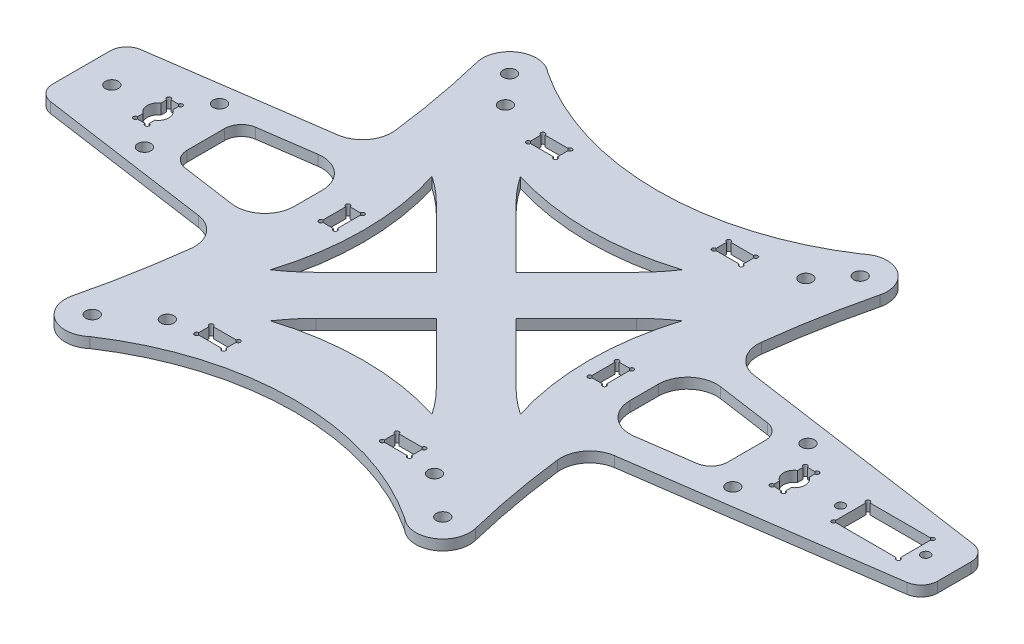
SolidWorks part; units mm, degrees
material "PPS"
ref_plane "前视基准面" through (0, 0, 0) normal (0, 0, 1) x (1, 0, 0)
ref_plane "上视基准面" through (0, 0, 0) normal (0, 1, 0) x (1, 0, 0)
ref_plane "右视基准面" through (0, 0, 0) normal (1, 0, 0) x (0, 0, -1)
sketch "草图1" plane through (0, 0, 0) normal (0, 1, 0) x (1, 0, 0)
  line L3 (-133.7177, 0) -> (146.3754, 0) construction
  line L56 (0, 96.0639) -> (0, -115.1457) construction
  line L65 (-25.5, 41.5) -> (-19, 41.5)
  line L66 (-34, 3.25) -> (-30.5, 3.25)
  line L70 (-34, 3.25) -> (-34, -3.25)
  line L76 (-34, -3.25) -> (-30.5, -3.25)
  line L80 (-30.5, 3.25) -> (-30.5, -3.25)
  line L81 (-25.5, -38) -> (-19, -38)
  line L82 (-25.5, -38) -> (-25.5, -41.5)
  line L83 (-25.5, -41.5) -> (-19, -41.5)
  line L84 (-19, -38) -> (-19, -41.5)
  line L85 (-19, 38) -> (-19, 41.5)
  line L86 (-25.5, 38) -> (-19, 38)
  line L142 (-25.5, 38) -> (-25.5, 41.5)
  line L143 (25.5, 38) -> (25.5, 41.5)
  line L144 (25.5, 38) -> (19, 38)
  line L145 (19, 38) -> (19, 41.5)
  line L146 (19, -38) -> (19, -41.5)
  line L147 (25.5, -41.5) -> (19, -41.5)
  line L148 (25.5, -38) -> (25.5, -41.5)
  line L149 (25.5, -38) -> (19, -38)
  line L150 (30.5, 3.25) -> (30.5, -3.25)
  line L151 (34, -3.25) -> (30.5, -3.25)
  line L152 (34, 3.25) -> (34, -3.25)
  line L153 (34, 3.25) -> (30.5, 3.25)
  line L154 (25.5, 41.5) -> (19, 41.5)
  line L155 (77.65, -2.1518) -> (77.65, -4)
  line L156 (74.85, 4) -> (77.65, 4)
  line L157 (74.85, 4) -> (74.85, 2.1768)
  line L158 (74.85, -4) -> (77.65, -4)
  line L159 (77.65, 4) -> (77.65, 2.1518)
  line L160 (74.85, -2.1768) -> (74.85, -4)
  line L161 (97.5, 7.6653) -> (97.5, -9.1503) construction
  line L162 (89.75, 4.1) -> (105.25, 4.1)
  line L163 (89.75, 4.1) -> (89.75, -4.1)
  line L164 (89.75, -4.1) -> (105.25, -4.1)
  line L165 (105.25, 4.1) -> (105.25, -4.1)
  line L166 (-97.5, 7.6653) -> (-97.5, -9.1503) construction
  line L171 (-74.85, -2.1768) -> (-74.85, -4)
  line L172 (-77.65, 4) -> (-77.65, 2.1518)
  line L173 (-74.85, -4) -> (-77.65, -4)
  line L174 (-74.85, 4) -> (-74.85, 2.1768)
  line L175 (-74.85, 4) -> (-77.65, 4)
  line L176 (-77.65, -2.1518) -> (-77.65, -4)
  line L177 (114.5911, 7.4683) -> (114.5911, -7.4683)
  line L178 (114.5911, 7.4683) -> (43.1936, 17.6463)
  line L179 (114.5911, -7.4683) -> (43.1936, -17.6463)
  line L183 (-23.978, 14.4296) -> (-9.5485, 0)
  line L184 (14.4296, 23.978) -> (0, 9.5485)
  line L185 (-23.978, -14.4296) -> (-9.5485, 0)
  line L186 (-14.4296, 23.978) -> (0, 9.5485)
  line L187 (23.978, -14.4296) -> (9.5485, 0)
  line L188 (23.978, 14.4296) -> (9.5485, 0)
  line L189 (-14.4296, -23.978) -> (0, -9.5485)
  line L190 (14.4296, -23.978) -> (0, -9.5485)
  line L191 (-94.5795, 10.321) -> (-94.5795, -10.321)
  line L192 (-43.1936, 17.6463) -> (-94.5795, 10.321)
  line L193 (-94.5795, -10.321) -> (-43.1936, -17.6463)
  line L195 (-64.75, -7.9571) -> (-64.75, 7.9571)
  line L196 (-64.75, 7.9571) -> (-40.25, 11.4497)
  line L197 (-40.25, 11.4497) -> (-40.25, -11.4497)
  line L198 (-64.75, -7.9571) -> (-40.25, -11.4497)
  line L199 (64.75, 7.9571) -> (40.25, 11.4497)
  line L200 (40.25, 11.4497) -> (40.25, -11.4497)
  line L201 (64.75, -7.9571) -> (40.25, -11.4497)
  line L202 (64.75, 7.9571) -> (64.75, -7.9571)
  circle A0 centre (-36, 43) radius 1.55
  circle A1 centre (-32, -42) radius 1.55
  circle A2 centre (32, -42) radius 1.55
  circle A3 centre (36, 43) radius 1.55
  circle A4 centre (42, 50) radius 1.55
  circle A5 centre (42, -50) radius 1.55
  circle A6 centre (-42, -50) radius 1.55
  circle A7 centre (-42, 50) radius 1.55
  arc A8 (74.85, 2.1768) -> (74.85, -2.1768) centre (76.2307, 0) ccw
  arc A9 (77.65, -2.1518) -> (77.65, 2.1518) centre (76.2307, 0) ccw
  circle A10 centre (107.7, 0) radius 1.05
  circle A11 centre (87.3, 0) radius 1.05
  circle A12 centre (-87.3, 0) radius 1.05 construction
  arc A14 (-77.65, -2.1518) -> (-77.65, 2.1518) centre (-76.2307, 0) cw
  arc A15 (-74.85, 2.1768) -> (-74.85, -2.1768) centre (-76.2307, 0) cw
  arc A18 (-37.7098, 54.831) -> (37.7098, 54.831) centre (0, 111.5317) ccw
  arc A20 (48.2756, 48.4632) -> (43.1936, 17.6463) centre (246.1791, 0) ccw
  arc A21 (48.2756, 48.4632) -> (37.7098, 54.831) centre (42, 50) ccw
  arc A22 (-37.7098, -54.831) -> (37.7098, -54.831) centre (0, -111.5317) cw
  arc A23 (48.2756, -48.4632) -> (43.1936, -17.6463) centre (246.1791, 0) cw
  arc A24 (48.2756, -48.4632) -> (37.7098, -54.831) centre (42, -50) cw
  arc A26 (-48.2756, -48.4632) -> (-37.7098, -54.831) centre (-42, -50) ccw
  arc A27 (-48.2756, -48.4632) -> (-43.1936, -17.6463) centre (-246.1791, 0) ccw
  arc A28 (-48.2756, 48.4632) -> (-37.7098, 54.831) centre (-42, 50) cw
  arc A30 (-48.2756, 48.4632) -> (-43.1936, 17.6463) centre (-246.1791, 0) cw
  arc A31 (-23.978, 14.4296) -> (-29.9602, 19.3706) centre (-52.8883, -14.4807) ccw
  arc A32 (-23.978, -14.4296) -> (-29.9602, -19.3706) centre (-52.8883, 14.4807) cw
  arc A33 (-29.9602, -19.3706) -> (-29.9602, 19.3706) centre (-91.9966, 0) ccw
  arc A34 (-14.4296, 23.978) -> (-19.3706, 29.9602) centre (14.4807, 52.8883) cw
  arc A35 (-19.3706, 29.9602) -> (19.3706, 29.9602) centre (0, 91.9966) ccw
  arc A36 (14.4296, 23.978) -> (19.3706, 29.9602) centre (-14.4807, 52.8883) ccw
  arc A37 (23.978, 14.4296) -> (29.9602, 19.3706) centre (52.8883, -14.4807) cw
  arc A38 (29.9602, 19.3706) -> (29.9602, -19.3706) centre (91.9966, 0) ccw
  arc A39 (23.978, -14.4296) -> (29.9602, -19.3706) centre (52.8883, 14.4807) ccw
  arc A40 (14.4296, -23.978) -> (19.3706, -29.9602) centre (-14.4807, -52.8883) cw
  arc A41 (19.3706, -29.9602) -> (-19.3706, -29.9602) centre (0, -91.9966) ccw
  arc A42 (-14.4296, -23.978) -> (-19.3706, -29.9602) centre (14.4807, -52.8883) ccw
  circle A43 centre (70.5, 9) radius 1.55
  circle A44 centre (70.5, -9) radius 1.55
  circle A45 centre (-70.5, -9) radius 1.55
  circle A46 centre (-70.5, 9) radius 1.55
  circle A47 centre (-87.3, 0) radius 1.55
  point P81 (-34, 0)
  point P118 (0, 0)
  point P140 (-40.25, 0)
  point P149 (-64.75, 0)
  dimension "D5" = 38
  dimension "D18" = 8.2
  dimension "D24" = 3.1
  dimension "D6" = 3.1
  dimension "D11" = 50
  dimension "D15" = 74.85
  dimension "D16" = 2.1
  dimension "D17" = 15.5
  dimension "D21" = 3.1
  dimension "D1" = 6.5
  dimension "D2" = 3.5
  dimension "D3" = 30.5
  dimension "D4" = 19
  dimension "D7" = 32
  dimension "D8" = 42
  dimension "D9" = 43
  dimension "D10" = 36
  dimension "D12" = 42
  dimension "D13" = 2.8
  dimension "D14" = 4
  dimension "D19" = 2.45
  dimension "D20" = 97.5
  dimension "D22" = 9
  dimension "D23" = 70.5
  dimension "D25" = 6.55
  dimension "D26" = 5.75
  dimension "D27" = 6.25
  dimension "D28" = 4
extrude "凸台-拉伸1" add sketch "草图1" along normal blind 2.5
fillet "圆角1" radius 4 8 edges at (114.5911, 1.25, -7.4683) (114.5911, 1.25, 7.4683) (-94.5795, 1.25, 10.321) (-94.5795, 1.25, -10.321) (-64.75, 1.25, 7.9571) (-64.75, 1.25, -7.9571) (64.75, 1.25, 7.9571) (64.75, 1.25, -7.9571)
fillet "圆角2" radius 7 8 edges at (43.1936, 1.25, -17.6463) (43.1936, 1.25, 17.6463) (-43.1936, 1.25, 17.6463) (-43.1936, 1.25, -17.6463) (40.25, 1.25, 11.4497) (40.25, 1.25, -11.4497) (-40.25, 1.25, 11.4497) (-40.25, 1.25, -11.4497)
sketch "草图2" plane through (0, 2.5, 0) normal (0, 1, 0) x (1, 0, 0)
  line L0 (0, 0) -> (0, -66.7571) construction
  circle A0 centre (-77.65, 4) radius 0.5
  circle A1 centre (-74.85, 4) radius 0.5
  circle A2 centre (-77.65, -4) radius 0.5
  circle A3 centre (-74.85, -4) radius 0.5
  circle A4 centre (-25.5, 41.5) radius 0.5
  circle A5 centre (-19, 41.5) radius 0.5
  circle A6 centre (-25.5, 38) radius 0.5
  circle A7 centre (-19, 38) radius 0.5
  circle A8 centre (-34, 3.25) radius 0.5
  circle A9 centre (-30.5, 3.25) radius 0.5
  circle A10 centre (-34, -3.25) radius 0.5
  circle A11 centre (-30.5, -3.25) radius 0.5
  circle A12 centre (-25.5, -38) radius 0.5
  circle A13 centre (-19, -38) radius 0.5
  circle A14 centre (-25.5, -41.5) radius 0.5
  circle A15 centre (-19, -41.5) radius 0.5
  circle A16 centre (19, -41.5) radius 0.5
  circle A17 centre (25.5, -41.5) radius 0.5
  circle A18 centre (19, -38) radius 0.5
  circle A19 centre (25.5, -38) radius 0.5
  circle A20 centre (30.5, -3.25) radius 0.5
  circle A21 centre (34, -3.25) radius 0.5
  circle A22 centre (30.5, 3.25) radius 0.5
  circle A23 centre (34, 3.25) radius 0.5
  circle A24 centre (19, 38) radius 0.5
  circle A25 centre (25.5, 38) radius 0.5
  circle A26 centre (19, 41.5) radius 0.5
  circle A27 centre (25.5, 41.5) radius 0.5
  circle A28 centre (74.85, -4) radius 0.5
  circle A29 centre (77.65, -4) radius 0.5
  circle A30 centre (74.85, 4) radius 0.5
  circle A31 centre (77.65, 4) radius 0.5
  circle A32 centre (89.75, 4.1) radius 0.5
  circle A33 centre (105.25, 4.1) radius 0.5
  circle A34 centre (89.75, -4.1) radius 0.5
  circle A35 centre (105.25, -4.1) radius 0.5
  dimension "D1" = 1
extrude "直角约束" cut sketch "草图2" against normal through all
